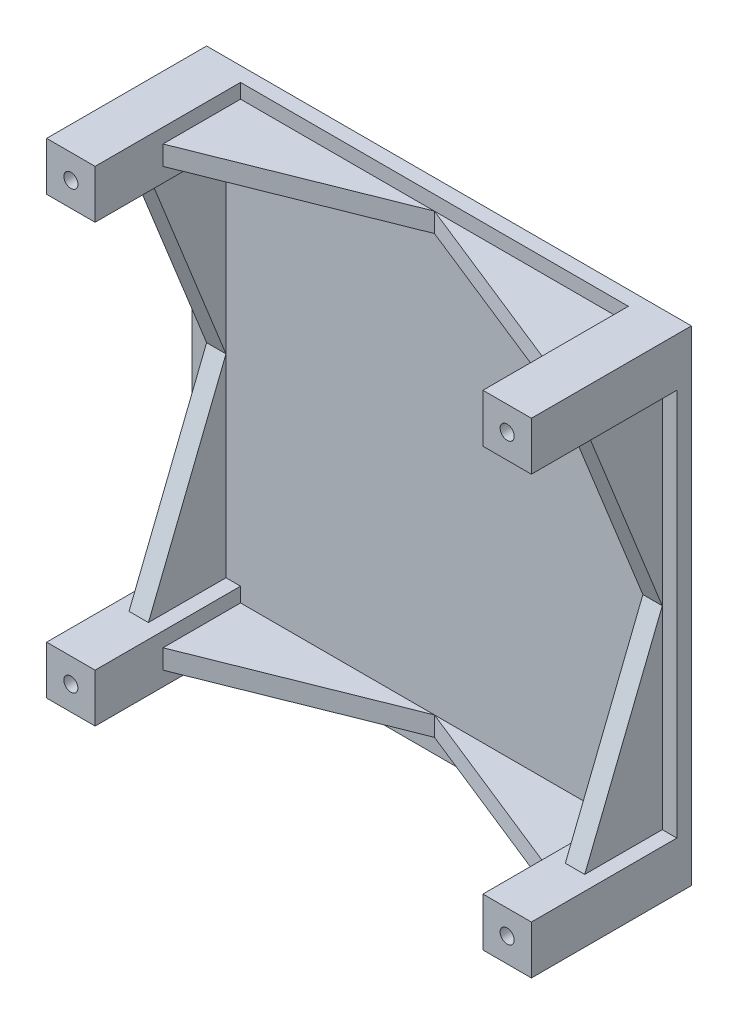
SolidWorks part; units mm, degrees
ref_plane "前视基准面" through (0, 0, 0) normal (0, 0, 1) x (1, 0, 0)
ref_plane "上视基准面" through (0, 0, 0) normal (0, 1, 0) x (1, 0, 0)
ref_plane "右视基准面" through (0, 0, 0) normal (1, 0, 0) x (0, 0, -1)
sketch "草图1" plane through (0, 0, 0) normal (0, 0, 1) x (1, 0, 0)
  line L1 (0, 0) -> (100, 0)
  line L2 (0, 0) -> (0, 100)
  line L3 (0, 100) -> (100, 100)
  line L4 (100, 0) -> (100, 100)
  line L7 (0, 10) -> (10, 10)
  line L8 (10, 0) -> (10, 10)
  line L11 (100, 10) -> (90, 10)
  line L12 (90, 0) -> (90, 10)
  line L15 (100, 90) -> (90, 90)
  line L16 (90, 100) -> (90, 90)
  line L19 (0, 90) -> (10, 90)
  line L20 (10, 100) -> (10, 90)
extrude "凸台-拉伸3" add sketch "草图1" along normal blind 3 contours L3 L20 L19 L2 L7 L8 L1 L12 L11 L4 L15 L16 region at (50, 50, 0)
extrude "凸台-拉伸4" add sketch "草图1<4>" along normal blind 33 contours L1 L8 L7 L2 | L20 L3 L2 L19 | L3 L16 L15 L4 | L12 L1 L4 L11 region at (5, 5, 0) region at (95, 5, 0) region at (5, 95, 0) region at (95, 95, 0)
sketch "草图1<4>" plane through (0, 0, 0) normal (0, 0, 1) x (1, 0, 0) same geometry as "草图1"
sketch "草图3" plane through (0, 0, 33) normal (0, 0, 1) x (1, 0, 0)
  line L0 (0, 100) -> (5, 100)
  line L1 (0, 100) -> (10, 100) construction
  line L2 (5, 100) -> (5, 95)
  circle A0 centre (5, 95) radius 1.45
extrude "切除-拉伸1" cut sketch "草图3" against normal blind 16 contours A0 region at (4.0037, 94.0037, 33)
sketch "草图4" plane through (0, 0, 33) normal (0, 0, 1) x (1, 0, 0)
  line L0 (90, 100) -> (95, 100)
  line L1 (90, 100) -> (100, 100) construction
  line L2 (95, 100) -> (95, 95)
  circle A0 centre (95, 95) radius 1.45
extrude "切除-拉伸2" cut sketch "草图4" against normal blind 16 contours A0 region at (94.0037, 94.0037, 33)
sketch "草图5" plane through (0, 0, 33) normal (0, 0, 1) x (1, 0, 0)
  line L0 (90, 10) -> (95, 10)
  line L1 (100, 10) -> (90, 10) construction
  line L2 (95, 10) -> (95, 5)
  line L3 (0, 0) -> (5, 0)
  line L4 (0, 0) -> (10, 0) construction
  line L5 (5, 0) -> (5, 5)
  circle A0 centre (95, 5) radius 1.45
  circle A1 centre (5, 5) radius 1.45
extrude "切除-拉伸3" cut sketch "草图5" against normal blind 16 contours A1 region at (5.9963, 4.0037, 33)
extrude "切除-拉伸4" cut sketch "草图5<3>" against normal blind 16 contours A0 region at (94.0037, 4.0037, 33)
sketch "草图5<3>" plane through (0, 0, 33) normal (0, 0, 1) x (1, 0, 0) same geometry as "草图5"
sketch "草图7" plane through (0, 0, 3) normal (0, 0, 1) x (1, 0, 0)
  line L0 (5, 10) -> (3, 10)
  line L1 (0, 10) -> (10, 10) construction
  line L2 (3, 10) -> (3, 90)
  line L3 (0, 90) -> (10, 90) construction
  line L4 (3, 90) -> (7, 90)
  line L5 (7, 90) -> (7, 10)
  line L6 (7, 10) -> (3, 10)
  line L7 (10, 95) -> (10, 97)
  line L8 (10, 100) -> (10, 90) construction
  line L9 (10, 97) -> (90, 97)
  line L10 (90, 100) -> (90, 90) construction
  line L11 (90, 97) -> (90, 93)
  line L12 (90, 93) -> (10, 93)
  line L13 (10, 93) -> (10, 97)
  line L14 (10, 5) -> (10, 7)
  line L15 (10, 0) -> (10, 10) construction
  line L16 (10, 7) -> (90, 7)
  line L17 (90, 0) -> (90, 10) construction
  line L18 (90, 7) -> (90, 3)
  line L19 (90, 3) -> (10, 3)
  line L20 (10, 3) -> (10, 7)
  line L21 (95, 10) -> (93, 10)
  line L22 (100, 10) -> (90, 10) construction
  line L23 (93, 10) -> (93, 90)
  line L24 (100, 90) -> (90, 90) construction
  line L25 (93, 90) -> (97, 90)
  line L26 (97, 90) -> (97, 10)
  line L27 (97, 10) -> (93, 10)
  line M9 (90, 10) -> (100, 10)
  line M11 (100, 90) -> (90, 90)
extrude "凸台-拉伸5" add sketch "草图7" along normal blind 16 contours L26 L23 M11 M9 | L16 L18 L19 L20 | L2 L4 L5 L6 | L9 L11 L12 L13 region at (95, 50, 3)
sketch "草图8" plane through (0, 7, 0) normal (0, 1, 0) x (1, 0, 0)
  line L0 (89.9102, -19) -> (50, -3)
  line L1 (10, -19) -> (90, -19) construction
  line L2 (10, -3) -> (90, -3) construction
  line L3 (50, -3) -> (10, -19)
  line L4 (10, -19) -> (89.9102, -19)
extrude "切除-拉伸5" cut sketch "草图8" against normal blind 16
sketch "草图9" plane through (7, 0, 0) normal (1, 0, 0) x (0, 0, -1)
  line L0 (-19, 10) -> (-3, 50)
  line L1 (-3, 90) -> (-3, 10) construction
  line L2 (-3, 50) -> (-19, 90)
  line L3 (-19, 90) -> (-19, 10)
extrude "切除-拉伸6" cut sketch "草图9" against normal blind 16
sketch "草图10" plane through (0, 93, 0) normal (0, -1, 0) x (1, 0, 0)
  line L0 (10, 19) -> (50, 3)
  line L1 (90, 3) -> (10, 3) construction
  line L2 (50, 3) -> (90, 19)
  line L3 (90, 19) -> (10, 19) construction
  line L4 (90, 19) -> (10, 19)
extrude "切除-拉伸7" cut sketch "草图10" against normal blind 16
sketch "草图11" plane through (93, 0, 0) normal (-1, 0, 0) x (0, 0, 1)
  line L0 (19, 90) -> (3, 50)
  line L1 (3, 10) -> (3, 90) construction
  line L2 (3, 50) -> (19, 10)
  line L3 (19, 10) -> (19, 90) construction
  line L4 (19, 10) -> (3, 10) construction
  line L5 (19, 10) -> (19, 90)
extrude "切除-拉伸8" cut sketch "草图11" against normal blind 16
